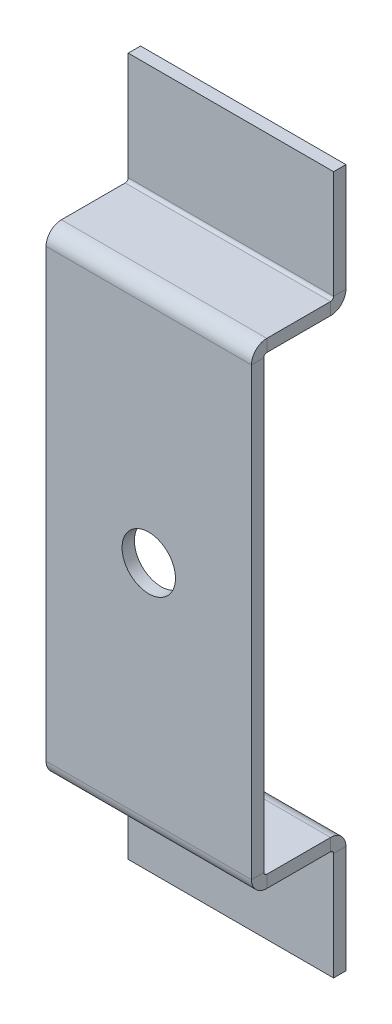
SolidWorks part; units mm, degrees
note: The reader was unsure of these and kept them because the rebuilt part matched: flange length of "边线-法兰1", "边线-法兰2".
ref_plane "前视基准面" through (0, 0, 0) normal (0, 0, 1) x (1, 0, 0)
ref_plane "上视基准面" through (0, 0, 0) normal (0, 1, 0) x (1, 0, 0)
ref_plane "右视基准面" through (0, 0, 0) normal (1, 0, 0) x (0, 0, -1)
other "Configuration Table"
sketch "草图1" plane through (0, 0, 0) normal (0, 0, 1) x (1, 0, 0)
  line L1 (0, 0) -> (50, 0)
  line L2 (0, 0) -> (0, 110)
  line L3 (0, 110) -> (50, 110)
  line L4 (50, 0) -> (50, 110)
  dimension "D1" = 110
  dimension "D2" = 50
base flange "基体-法兰1" sketch "草图1" thickness 3 reverse thickness direction no parameters "D1"=0.7366
edge flange "边线-法兰1" sketch "草图10" flange profiles "草图10", "草图11" flange angle 90 flange length 20 flange position material outside bend radius 0.7366 thickness 3 relief rectangular parameters "D6"=10, "D8"=1
sketch "草图10" plane through (0, 110, -3) normal (0, -1, 0) x (-1, 0, 0)
  line L2 (-50, 0) -> (-50, 17)
  line L3 (-50, 17) -> (0, 17)
  line L4 (0, 17) -> (0, 0)
  line L5 (0, 0) -> (-50, 0) construction
  line L6 (0, 0) -> (-50, 0)
sketch "草图11" plane through (0, 0, -3) normal (0, 1, 0) x (1, 0, 0)
  line L0 (50, 0) -> (0, 0) construction
  line L1 (50, 0) -> (0, 0)
  line L2 (50, 0) -> (50, 17)
  line L3 (50, 17) -> (0, 17)
  line L4 (0, 17) -> (0, 0)
bend "边线折弯1" bend radius 0.7366 bend angle 90 parameters "D5"=1
bend "边线折弯2" bend radius 0.7366 bend angle 90 parameters "D5"=2
edge flange "边线-法兰2" sketch "草图16" flange profiles "草图16", "草图17" flange angle 90 flange length 30 flange position material outside bend radius 0.7366 thickness 3 relief rectangular parameters "D6"=10, "D8"=1
sketch "草图16" plane through (0, -3, -20) normal (0, 0, -1) x (1, 0, 0)
  line L2 (0, 0) -> (0, 27)
  line L3 (0, 27) -> (50, 27)
  line L4 (50, 27) -> (50, 0)
  line L7 (50, 0) -> (0, 0) construction
  line L8 (50, 0) -> (0, 0)
sketch "草图17" plane through (0, 113, -20) normal (0, 0, -1) x (-1, 0, 0)
  line L0 (0, 0) -> (-50, 0) construction
  line L1 (0, 0) -> (-50, 0)
  line L2 (-50, 0) -> (-50, 27)
  line L3 (-50, 27) -> (0, 27)
  line L4 (0, 27) -> (0, 0)
bend "边线折弯3" bend radius 0.7366 bend angle 90 parameters "D5"=3
bend "边线折弯4" bend radius 0.7366 bend angle 90 parameters "D5"=4
sketch "草图18" plane through (0, 0, 0) normal (0, 0, 1) x (1, 0, 0)
  line L7 (50, -30) -> (0, -30) construction
  line L8 (50, 0.7366) -> (50, 109.2634) construction
  circle A0 centre (25, 55) radius 6.5
  dimension "D5" = 13
  dimension "D3" = 85
  dimension "D4" = 25
extrude "切除-拉伸1" cut sketch "草图18" against normal through all normal cut yes
sketch "折弯-线1" plane through (0, 0, 0) normal (0, 1, 0) x (1, 0, 0)
sketch "边界框1" plane through (0, 0, 0) normal (0, 1, 0) x (1, 0, 0)
sheet metal parameters "钣金6" thickness 3 parameters "D1"=0.7366
flat pattern "平板型式6" [suppressed]
sketch "折弯-线2" plane through (0, 0, 0) normal (0, 1, 0) x (1, 0, 0)
sketch "边界框2" [suppressed] plane through (0, 0, 0) normal (0, 1, 0) x (1, 0, 0)
sheet metal parameters "钣金7" thickness 3 parameters "D1"=0.7366
flat pattern "平板型式6" [suppressed]
sketch "折弯-线2" plane through (0, 0, 0) normal (0, 1, 0) x (1, 0, 0)
sketch "边界框2" [suppressed] plane through (0, 0, 0) normal (0, 1, 0) x (1, 0, 0)
bend of the flat pattern "展平-<边线折弯1>1"
bend of the flat pattern "展平-<边线折弯2>1"
sheet metal parameters "钣金8" thickness 3 parameters "D1"=0.7366
flat pattern "平板型式6" [suppressed]
sketch "折弯-线2" plane through (0, 0, 0) normal (0, 1, 0) x (1, 0, 0)
sketch "边界框2" [suppressed] plane through (0, 0, 0) normal (0, 1, 0) x (1, 0, 0)
bend of the flat pattern "展平-<边线折弯1>1"
bend of the flat pattern "展平-<边线折弯2>1"
bend of the flat pattern "展平-<边线折弯3>1"
bend of the flat pattern "展平-<边线折弯4>1"
sheet metal parameters "钣金9" thickness 3 parameters "D1"=0.7366
flat pattern "平板型式6" [suppressed]
sketch "折弯-线2" plane through (0, 0, 0) normal (0, 1, 0) x (1, 0, 0)
sketch "边界框2" [suppressed] plane through (0, 0, 0) normal (0, 1, 0) x (1, 0, 0)
bend of the flat pattern "展平-<边线折弯1>1"
bend of the flat pattern "展平-<边线折弯2>1"
bend of the flat pattern "展平-<边线折弯3>1"
bend of the flat pattern "展平-<边线折弯4>1"
